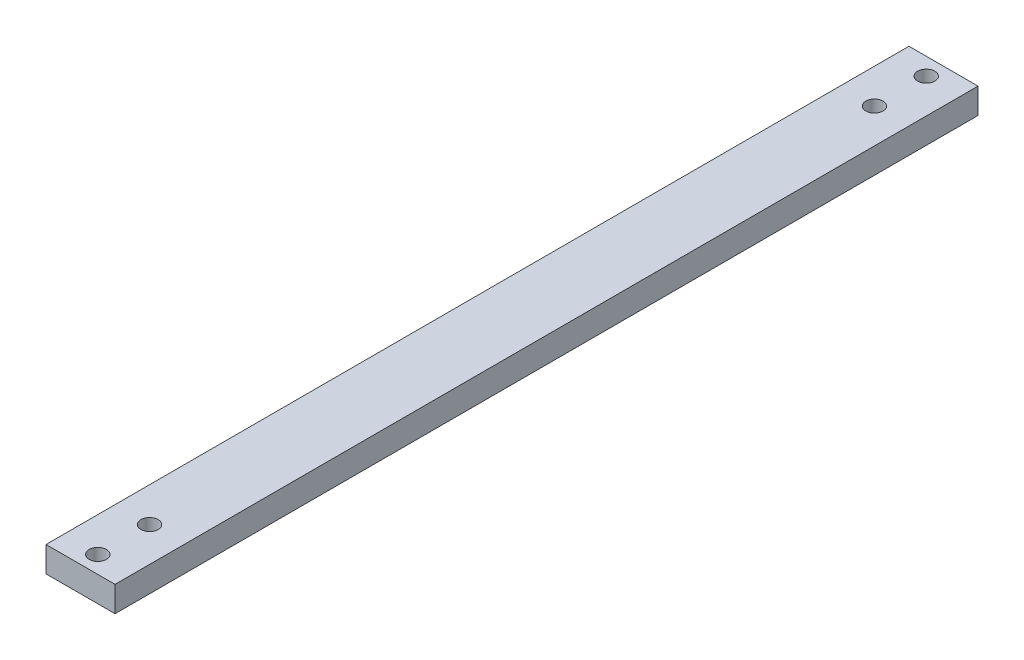
SolidWorks part; units mm, degrees
ref_plane "前视基准面" through (0, 0, 0) normal (0, 0, 1) x (1, 0, 0)
ref_plane "上视基准面" through (0, 0, 0) normal (0, 1, 0) x (1, 0, 0)
ref_plane "右视基准面" through (0, 0, 0) normal (1, 0, 0) x (0, 0, -1)
other "Configuration Table"
sketch "草图1" plane through (0, 0, 0) normal (0, 1, 0) x (1, 0, 0)
  line L1 (0, 0) -> (8, 0)
  line L2 (0, 0) -> (0, -100)
  line L3 (0, -100) -> (8, -100)
  line L4 (8, 0) -> (8, -100)
  dimension "D1" = 100
  dimension "D2" = 8
extrude "凸台-拉伸1" add sketch "草图1" along normal blind 2.95
sketch "草图2" plane through (0, 2.95, 0) normal (0, 1, 0) x (1, 0, 0)
  line L0 (0, -2) -> (8, -2)
  line L1 (0, 0) -> (0, -100) construction
  line L2 (8, -100) -> (8, 0) construction
  line L3 (8, 0) -> (0, 0) construction
  line L4 (0, -100) -> (8, -100) construction
  circle A0 centre (4, -8) radius 0.7
  circle A1 centre (4, -8) radius 1
  circle A2 centre (4, -2) radius 0.7
  circle A3 centre (4, -2) radius 1
  circle A4 centre (4, -98) radius 0.7
  circle A5 centre (4, -98) radius 1
  circle A6 centre (4, -92) radius 0.7
  circle A7 centre (4, -92) radius 1
  dimension "D1" = 2
  dimension "D2" = 1.4
  dimension "D3" = 2
  dimension "D4" = 1.4
  dimension "D7" = 2
  dimension "D8" = 1.4
  dimension "D9" = 2
  dimension "D10" = 1.4
  dimension "D5" = 2
  dimension "D6" = 6
  dimension "D11" = 2
  dimension "D12" = 6
extrude "切除-拉伸1" cut sketch "草图2" against normal through all contours A2 | A0 | A6 | A4
extrude "切除-拉伸2" cut sketch "草图2<3>" against normal blind 1.5 contours A1 | A3 | A5 | A7
sketch "草图2<3>" plane through (0, 2.95, 0) normal (0, 1, 0) x (1, 0, 0) same geometry as "草图2"
